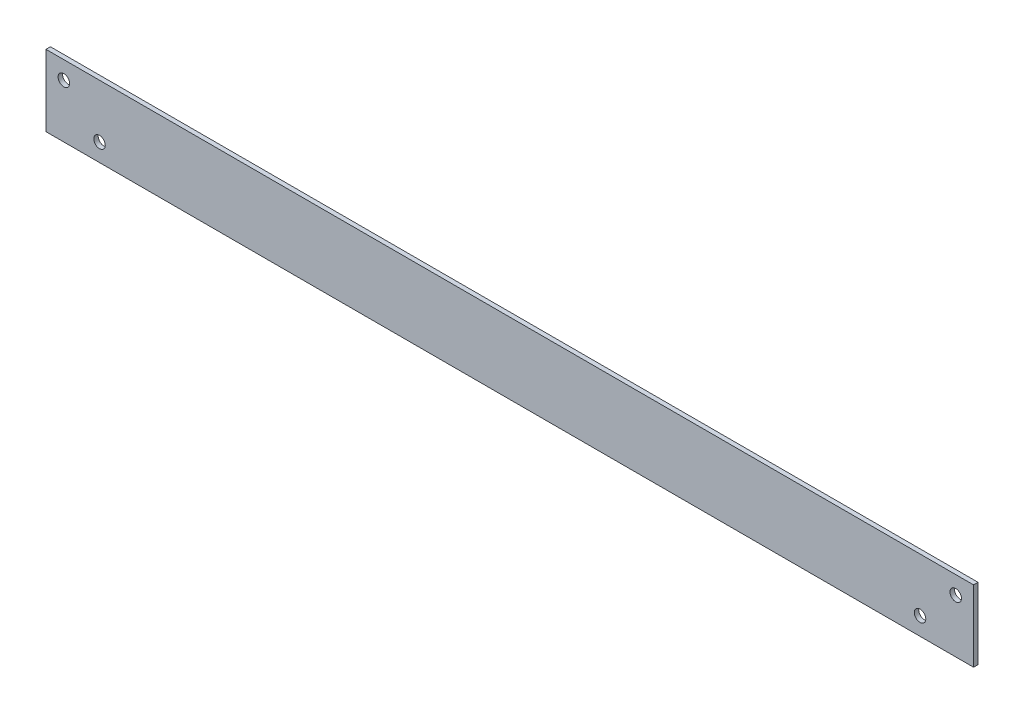
SolidWorks part; units mm, degrees
ref_plane "Front Plane" through (0, 0, 0) normal (0, 0, 1) x (1, 0, 0)
ref_plane "Top Plane" through (0, 0, 0) normal (0, 1, 0) x (1, 0, 0)
ref_plane "Right Plane" through (0, 0, 0) normal (1, 0, 0) x (0, 0, -1)
sketch "Sketch1" plane through (0, 0, 0) normal (0, 0, 1) x (1, 0, 0)
  line L0 (-174.625, 12.7) -> (-139.7, 12.7)
  line L1 (165.1, -12.7) -> (-165.1, -12.7)
  line L2 (165.1, -12.7) -> (165.1, 12.7)
  line L3 (165.1, 12.7) -> (-165.1, 12.7)
  line L4 (-165.1, -12.7) -> (-165.1, 12.7)
  line L5 (165.1, -12.7) -> (-165.1, 12.7) construction
  line L6 (165.1, 12.7) -> (-165.1, -12.7) construction
  line L7 (-139.7, 12.7) -> (-139.7, -12.7)
  line L8 (-139.7, -12.7) -> (-174.625, -12.7)
  line L9 (-165.1, 11.1125) -> (-88.6699, 11.1125) construction
  line L10 (-174.625, 12.7) -> (-174.625, 8) construction
  line L11 (0, 12.7) -> (0, -12.7) construction
  line L12 (139.7, 12.7) -> (139.7, -12.7)
  line L13 (165.1, 12.7) -> (177.4902, 15.4878)
  line L14 (165.1, -12.7) -> (177.4902, -15.4878)
  circle A0 centre (-174.625, 0) radius 8
  circle A1 centre (-174.625, 0) radius 12.7
  circle A2 centre (-158.75, 6.35) radius 2.05
  circle A3 centre (-146.05, -6.35) radius 2.05
  circle A7 centre (180.975, 0) radius 11.1125
  circle A8 centre (180.975, 0) radius 15.875
  circle A9 centre (146.05, -6.35) radius 2.05
  circle A10 centre (158.75, 6.35) radius 2.05
  point P0 (0, 0)
  point P25 (0, 0)
  dimension "D3" = 16
  dimension "D6" = 4.1
  dimension "D12" = 22.225
  dimension "D14" = 31.75
  dimension "D1" = 330.2
  dimension "D2" = 25.4
  dimension "D4" = 174.625
  dimension "D5" = 25.4
  dimension "D7" = 6.35
  dimension "D8" = 1.5875
  dimension "D9" = 6.35
  dimension "D10" = 6.35
  dimension "D11" = 6.35
  dimension "D13" = 180.975
extrude "Boss-Extrude1" add sketch "Sketch1" along normal blind 1.5875 contours A1 L4 L1 L7 L0 A3 A2 | L12 L3 L7 L1 | L3 L12 L1 L2 A9 A10 | L4 A1 region at (-151.6832, 0, 0) region at (-163.8153, 0, 0) region at (0, 0, 0) region at (152.4, 0, 0)
fillet "Fillet1" radius 1.5875 rebuild error yes
